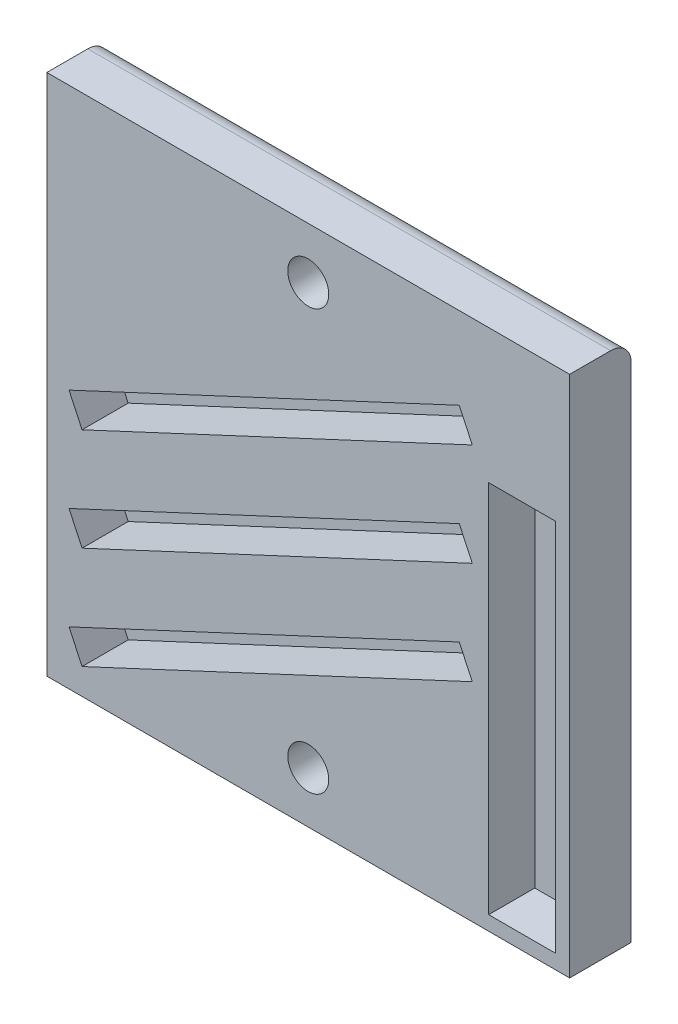
SolidWorks part; units mm, degrees
material "ABS"
ref_plane "Plano frontal" through (0, 0, 0) normal (0, 0, 1) x (1, 0, 0)
ref_plane "Plano superior" through (0, 0, 0) normal (0, 1, 0) x (1, 0, 0)
ref_plane "Plano direito" through (0, 0, 0) normal (1, 0, 0) x (0, 0, -1)
sketch "Esboço1" plane through (0, 0, 0) normal (0, 0, 1) x (1, 0, 0)
  line L1 (25.5, 25.5) -> (-25.5, 25.5)
  line L2 (25.5, 25.5) -> (25.5, -25.5)
  line L3 (25.5, -25.5) -> (-25.5, -25.5)
  line L4 (-25.5, 25.5) -> (-25.5, -25.5)
  line L5 (25.5, 25.5) -> (-25.5, -25.5) construction
  line L6 (25.5, -25.5) -> (-25.5, 25.5) construction
  point P0 (0, 0)
  dimension "D1" = 51
  dimension "D2" = 51
extrude "Ressalto-extrusão1" add sketch "Esboço1" along normal blind 6
sketch "Esboço2" plane through (0, 0, 0) normal (0, 0, -1) x (-1, 0, 0)
  line L0 (25.5, -25.5) -> (-25.5, -25.5) construction
  line L1 (-24.1, 12.4) -> (-17.6, 12.4)
  line L2 (-24.1, 12.4) -> (-24.1, -24.1)
  line L3 (-24.1, -24.1) -> (-17.6, -24.1)
  line L4 (-17.6, 12.4) -> (-17.6, -24.1)
  line L5 (-25.5, -25.5) -> (-25.5, 25.5) construction
  dimension "D1" = 6.5
  dimension "D2" = 36.5
  dimension "D3" = 1.4
  dimension "D4" = 1.4
extrude "Corte-extrusão1" cut sketch "Esboço2" against normal blind 4.5
sketch "Esboço3" plane through (0, 0, 6) normal (0, 0, 1) x (1, 0, 0)
  line L0 (25.5, 25.5) -> (-25.5, 25.5) construction
  line L1 (-25.5, -25.5) -> (25.5, -25.5) construction
  circle A0 centre (0, -20.5) radius 2
  circle A1 centre (0, 20.5) radius 2
  dimension "D1" = 4
  dimension "D2" = 5
  dimension "D3" = 5
extrude "Corte-extrusão2" cut sketch "Esboço3" against normal through all
sketch "Esboço4" plane through (0, 0, 0) normal (0, 0, -1) x (-1, 0, 0)
  line L1 (-14.7321, 17.5) -> (23.3328, -0.25)
  line L2 (-14.7321, 17.5) -> (-16, 14.7811)
  line L3 (-16, 14.7811) -> (22.0649, -2.9689)
  line L4 (23.3328, -0.25) -> (22.0649, -2.9689)
  line L6 (25.5, -25.5) -> (-25.5, -25.5) construction
  line L9 (-25.5, -25.5) -> (-25.5, 25.5) construction
  line L10 (-25.5, 25.5) -> (25.5, 25.5) construction
  dimension "D1" = 3
  dimension "D2" = 25
  dimension "D3" = 42
  dimension "D4" = 9.5
  dimension "D5" = 8
extrude "Corte-extrusão3" cut sketch "Esboço4" against normal up to surface (4.5 mm away) up to face at (20.85, -5.85, 4.5)
pattern_linear "Padrão linear1" count 3 spacing 10 along (0, -1, 0) of "Corte-extrusão3"
fillet "Filete1" radius 2 1 edges at (0, 25.5, 6)
chamfer "Chanfro1" distance 1 angle 45 2 edges at (2, -20.5, 6) (2, 20.5, 6)
mirror "Espelhar1" about plane through (0, 0, 0) normal (0, 0, 1) of bodies 107
delete or keep bodies "Corpo-Excluir/Manter 1" type delete bodies bodies 107
